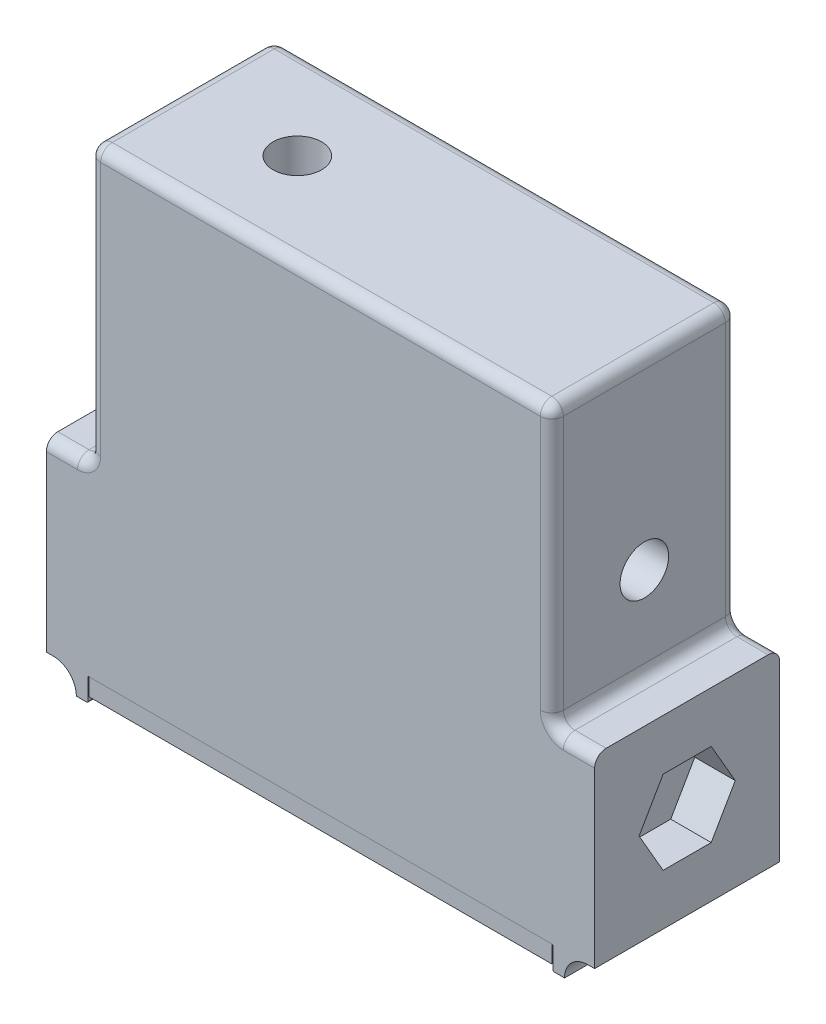
SolidWorks part; units mm, degrees
other "Gasket (DISABLE WHEN 3D PRINTING)" parameters "D1"=40, "D2"=18.2927
ref_plane "Front Plane" through (0, 0, 0) normal (0, 0, 1) x (1, 0, 0)
ref_plane "Top Plane" through (0, 0, 0) normal (0, 1, 0) x (1, 0, 0)
ref_plane "Right Plane" through (0, 0, 0) normal (1, 0, 0) x (0, 0, -1)
sketch "Sketch1" plane through (0, 0, 0) normal (0, 1, 0) x (1, 0, 0)
  line L1 (-20, 8) -> (20, 8)
  line L2 (-20, 8) -> (-20, -8)
  line L3 (-20, -8) -> (20, -8)
  line L4 (20, 8) -> (20, -8)
  line L5 (-20, 8) -> (20, -8) construction
  line L6 (-20, -8) -> (20, 8) construction
  point P4 (0, 0)
  dimension "D1" = 40
  dimension "D2" = 16
extrude "Body" add sketch "Sketch1" along normal blind 40
sketch "Sketch2" plane through (0, 0, 0) normal (0, 1, 0) x (1, 0, 0)
  line L0 (0, -24.6326) -> (0, 25.7324) construction
  line L1 (-20, -8) -> (-23.7, -8)
  line L2 (-20, -8) -> (-20, 8)
  line L3 (-20, 8) -> (-23.7, 8)
  line L4 (-23.7, -8) -> (-23.7, 8)
  line L5 (-20, -8) -> (-23.7, 8) construction
  line L6 (-20, 8) -> (-23.7, -8) construction
  line L7 (20, 8) -> (23.7, 8)
  line L8 (23.7, -8) -> (23.7, 8)
  line L9 (20, -8) -> (23.7, -8)
  line L10 (20, -8) -> (20, 8)
  point P4 (-21.85, 0)
  dimension "D1" = 3.7
extrude "Extension" add sketch "Sketch2" along normal blind 16
sketch "Nut Alignment Sketch" plane through (0, 0, 0) normal (1, 0, 0) x (0, 0, -1)
  line L0 (-8, 16) -> (8, 0) construction
  circle A0 centre (0, 8) radius 2.5 construction
  dimension "D1" = 5
sketch "Sketch5" plane through (0, 0, 0) normal (0, 1, 0) x (1, 0, 0)
  line L1 (-17, -5) -> (17, -5)
  line L2 (-17, -5) -> (-17, 5)
  line L3 (-17, 5) -> (17, 5)
  line L4 (17, -5) -> (17, 5)
  line L5 (-17, -5) -> (17, 5) construction
  line L6 (-17, 5) -> (17, -5) construction
  line L7 (-20, 8) -> (-20, -8) construction
  line L8 (-23.7, -8) -> (23.7, -8) construction
  line L9 (-20, 8) -> (-20, -8) construction
  point P4 (0, 0)
  dimension "D1" = 3
  dimension "D2" = 3
extrude "Cavity" cut sketch "Sketch5" along normal blind 37
sketch "Sketch6" plane through (0, 40, 0) normal (0, 1, 0) x (1, 0, 0)
  line L0 (0, 5.2625) -> (0, 72.0397) construction
  line L1 (-26.607, 0) -> (21.944, 0) construction
  circle A0 centre (-10, 0) radius 2.1
  dimension "D2" = 4.2
  dimension "D1" = 10
extrude "Top Hole" cut sketch "Sketch6" against normal up to next
sketch "Sketch7" plane through (20, 0, 0) normal (1, 0, 0) x (0, 0, -1)
  line L0 (-8, 28) -> (8, 28) construction
  line L1 (-8, 40) -> (-8, 16) construction
  line L2 (8, 40) -> (8, 16) construction
  line L4 (0, 41.5439) -> (0, 6.2839) construction
  circle A0 centre (0, 24) radius 2.1
  dimension "D2" = 4.2
  dimension "D1" = 4
extrude "Side Hole" cut sketch "Sketch7" against normal up to next
sketch "Sketch3" plane through (0, 0, 0) normal (0, 1, 0) x (1, 0, 0)
  line L0 (-23.7, -8) -> (23.7, -8) construction
  line L1 (-21.1, -8) -> (-20.1, -8)
  line L2 (-21.1, -8) -> (-21.1, 8)
  line L3 (-21.1, 8) -> (-20.1, 8)
  line L4 (-20.1, -8) -> (-20.1, 8)
  line L5 (-21.1, -8) -> (-20.1, 8) construction
  line L6 (-21.1, 8) -> (-20.1, -8) construction
  line L7 (23.7, 8) -> (-23.7, 8) construction
  line L8 (0, -26.2727) -> (0, 27.5208) construction
  line L9 (-23.7, 8) -> (-23.7, -8) construction
  line L10 (23.7, -8) -> (23.7, 8) construction
  line L11 (21.1, 8) -> (20.1, 8)
  line L12 (20.1, -8) -> (20.1, 8)
  line L13 (21.1, -8) -> (20.1, -8)
  line L14 (21.1, -8) -> (21.1, 8)
  point P4 (-20.6, 0)
  dimension "D1" = 1
  dimension "D2" = 20.1
  dimension "D3" = 23.7
  dimension "D4" = 23.7
extrude "Legs" add sketch "Sketch3" against normal blind 2
sketch "Sketch4" plane through (-23.7, 0, 0) normal (-1, 0, 0) x (0, 0, 1)
  line L0 (-8, 16) -> (8, 0) construction
  line L2 (2.0785, 11.6) -> (-2.0785, 11.6)
  line L3 (-2.0785, 11.6) -> (-4.1569, 8)
  line L4 (-4.1569, 8) -> (-2.0785, 4.4)
  line L5 (-2.0785, 4.4) -> (2.0785, 4.4)
  line L6 (2.0785, 4.4) -> (4.1569, 8)
  line L7 (4.1569, 8) -> (2.0785, 11.6)
  circle A0 centre (0, 8) radius 3.6 construction
  dimension "D1" = 7.2
extrude "Mount Counterbore" cut sketch "Sketch4" against normal blind 3.5
mirror "Mount Counterbore Mirror" about plane through (0, 0, 0) normal (1, 0, 0) of "Mount Counterbore"
fillet "2mm Leg Fillet" radius 2 6 edges at (-21.1, -1, 8) (-21.1, -1, -8) (-21.1, 0, 0) (21.1, -1, -8) (21.1, -1, 8) (21.1, 0, 0)
fillet "0.1mm Leg Fillet" radius 0.1 4 edges at (20.1, 0, 0) (20.1, -2, 0) (-20.1, -2, 0) (-20.1, 0, 0)
fillet "Outer Boundary Fillet" radius 1 14 edges at (-20, 16, 0) (-21.85, 16, -8) (-20, 28, -8) (-20, 40, 0) (0, 40, -8) (20, 40, 0) (20, 28, -8) (21.85, 16, -8) (20, 16, 0) (-21.85, 16, 8) (-20, 28, 8) (0, 40, 8) (20, 28, 8) (21.85, 16, 8)
fillet "Inner Boundary Fillet" radius 1 8 edges at (17, 18.5, -5) (-17, 18.5, 5) (-17, 18.5, -5) (0, 37, -5) (-17, 37, 0) (0, 37, 5) (17, 37, 0) (17, 18.5, 5)
sketch "Sketch8" plane through (0, 0, 0) normal (0, -1, 0) x (1, 0, 0)
  line L4 (-16, -5) -> (16, -5)
  line L5 (-17, 4) -> (-17, -4)
  line L6 (16, 5) -> (-16, 5)
  line L7 (17, -4) -> (17, 4)
  line L8 (-16, -5) -> (16, -5)
  line L9 (-17, 4) -> (-17, -4)
  line L10 (16, 5) -> (-16, 5)
  line L11 (17, -4) -> (17, 4)
  line L12 (-20, -8) -> (20, -8)
  line L13 (20, -8) -> (20, 8)
  line L14 (20, 8) -> (-20, 8)
  line L15 (-20, 8) -> (-20, -8)
  line L16 (-20, -8) -> (20, -8)
  line L17 (20, -8) -> (20, 8)
  line L18 (20, 8) -> (-20, 8)
  line L19 (-20, 8) -> (-20, -8)
  arc A4 (-17, -4) -> (-16, -5) centre (-16, -4) ccw
  arc A5 (-17, -4) -> (-16, -5) centre (-16, -4) ccw
  arc A6 (-16, 5) -> (-17, 4) centre (-16, 4) ccw
  arc A7 (-16, 5) -> (-17, 4) centre (-16, 4) ccw
  arc A12 (17, 4) -> (16, 5) centre (16, 4) ccw
  arc A13 (17, 4) -> (16, 5) centre (16, 4) ccw
  arc A14 (16, -5) -> (17, -4) centre (16, -4) ccw
  arc A15 (16, -5) -> (17, -4) centre (16, -4) ccw
  dimension "D1" = 0
  dimension "D2" = 0
extrude "Boss-Extrude1" add sketch "Sketch8" along normal blind 1.5 separate body
equation "\"Height\"= 40mm"
equation "\"D1@Body\"=\"Height\""
equation "\"Length\"= 40mm"
equation "\"Width\"= 16"
equation "\"D2@Sketch1\"=\"Width\""
equation "\"D1@Sketch1\"=\"Length\""
equation "\"D1@Cavity\" = \"Height\" - 3mm"
